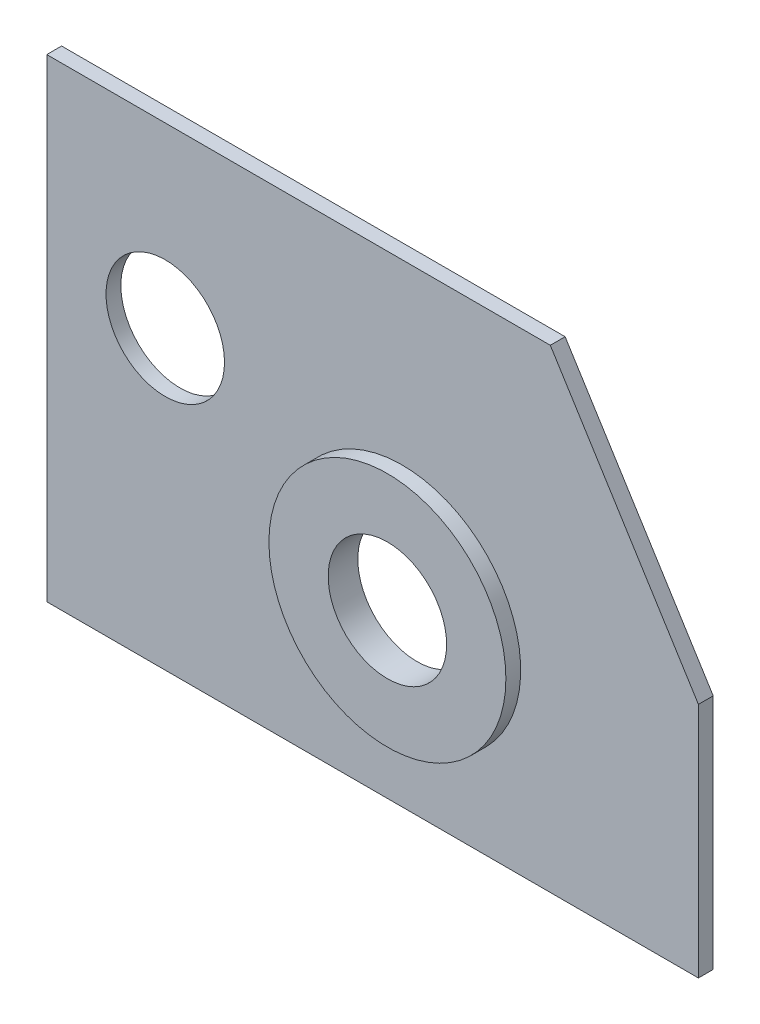
SolidWorks part; units mm, degrees
ref_plane "Front Plane" through (0, 0, 0) normal (0, 0, 1) x (1, 0, 0)
ref_plane "Top Plane" through (0, 0, 0) normal (0, 1, 0) x (1, 0, 0)
ref_plane "Right Plane" through (0, 0, 0) normal (1, 0, 0) x (0, 0, -1)
sketch "Sketch1" plane through (0, 0, 0) normal (0, 0, 1) x (1, 0, 0)
  line L1 (0, 0) -> (139.7, 0)
  line L2 (0, 0) -> (0, 101.6)
  line L3 (0, 101.6) -> (139.7, 101.6)
  line L4 (139.7, 0) -> (139.7, 101.6)
  dimension "D1" = 101.6
  dimension "D2" = 139.7
extrude "Boss-Extrude1" add sketch "Sketch1" along normal blind 3.175
sketch "Sketch2" plane through (0, 0, 3.175) normal (0, 0, 1) x (1, 0, 0)
  line L0 (107.95, 101.6) -> (139.7, 50.8)
  line L1 (139.7, 101.6) -> (0, 101.6) construction
  line L2 (139.7, 0) -> (139.7, 101.6) construction
  line L3 (0, 101.6) -> (0, 0) construction
  line L4 (0, 0) -> (139.7, 0) construction
  dimension "D1" = 107.95
  dimension "D2" = 50.8
extrude "Cut-Extrude1" cut sketch "Sketch2" against normal blind 3.175 and the other way through all
hole_wizard "1 (1) Diameter Hole1" positions "Sketch3" profile "Sketch4" hole size "1" standard "ANSI Inch" end condition through all
sketch "Sketch3" plane through (0, 0, 3.175) normal (0, 0, 1) x (1, 0, 0)
  line L0 (0, 101.6) -> (0, 0) construction
  line L1 (0, 0) -> (139.7, 0) construction
  point P0 (25.4, 63.5)
  dimension "D1" = 25.4
  dimension "D2" = 63.5
sketch "Sketch4" plane through (25.4, 63.5, 3.175) normal (1, 0, 0) x (0, -1, 0)
  line L0 (0, 0) -> (0, 3.175)
  line L1 (0, 3.175) -> (12.7, 3.175)
  line L2 (12.7, 3.175) -> (12.7, 0)
  line L5 (12.7, 0) -> (0, 0)
  line L11 (0, -6.35) -> (0, 107.95) construction
  dimension "Thru Hole Dia." = 25.4
  dimension "Thru Hole Depth" = 3.175
sketch "Sketch5" plane through (0, 0, 3.175) normal (0, 0, 1) x (1, 0, 0)
  line L0 (0, 101.6) -> (0, 0) construction
  line L1 (0, 0) -> (139.7, 0) construction
  circle A0 centre (76.2, 38.1) radius 25.4
  dimension "D1" = 50.8
  dimension "D2" = 76.2
  dimension "D3" = 38.1
extrude "Boss-Extrude2" add sketch "Sketch5" along normal blind 3.175
sketch "Sketch6" plane through (0, 0, 6.35) normal (0, 0, 1) x (1, 0, 0)
  circle A0 centre (76.2, 38.1) radius 12.7
extrude "Cut-Extrude2" cut sketch "Sketch6" against normal through all
